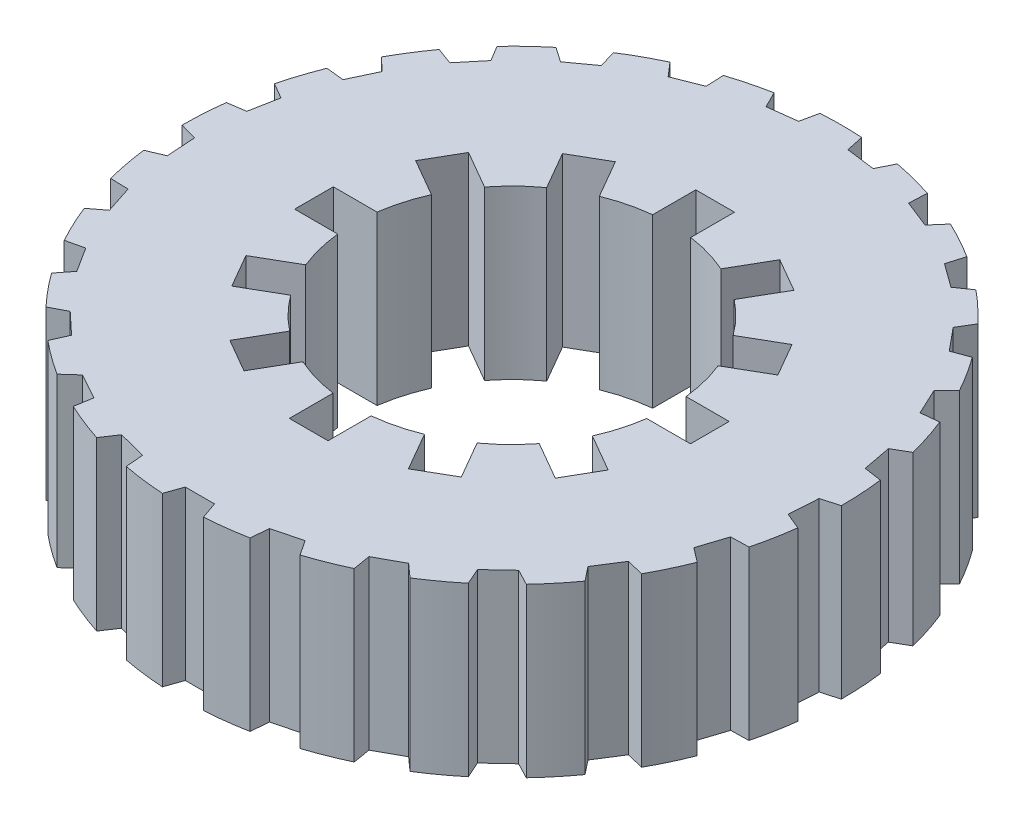
SolidWorks part; units mm, degrees
ref_plane "Front Plane" through (0, 0, 0) normal (0, 0, 1) x (1, 0, 0)
ref_plane "Top Plane" through (0, 0, 0) normal (0, 1, 0) x (1, 0, 0)
ref_plane "Right Plane" through (0, 0, 0) normal (1, 0, 0) x (0, 0, -1)
sketch "Sketch1" plane through (0, 0, 0) normal (0, 1, 0) x (1, 0, 0)
  circle A0 centre (0, 0) radius 37.465
extrude "Boss-Extrude1" add sketch "Sketch1" along normal blind 19.05
sketch "Sketch2" plane through (0, 0, 0) normal (0, -1, 0) x (1, 0, 0)
  line L10 (0, 37.465) -> (-2.36, 37.465)
  line L11 (0, 37.465) -> (2.36, 37.465)
  line L12 (0, 35.465) -> (-1.66, 35.465)
  line L13 (0, 35.465) -> (1.66, 35.465)
  line L14 (-2.36, 37.465) -> (-1.66, 35.465)
  line L15 (2.36, 37.465) -> (1.66, 35.465)
  circle A0 centre (0, 0) radius 37.465 construction
  dimension "D1" = 2.36
  dimension "D2" = 2.36
  dimension "D3" = 1.66
  dimension "D4" = 1.66
  dimension "D5" = 2
extrude "Cut-Extrude1" cut sketch "Sketch2" against normal blind 33
pattern_circular "CirPattern1" count 25 over 360 about axis through (0, 0, 0) along (0, 1, 0) of "Cut-Extrude1"
sketch "Sketch3" plane through (0, 19.05, 0) normal (0, 1, 0) x (1, 0, 0)
  line L16 (-1.9, 22.8) -> (-1.9, 17.8994)
  line L17 (0.3, 22.8) -> (-1.9, 22.8)
  line L18 (0.3, 22.8) -> (2.5, 22.8)
  line L19 (2.5, 22.8) -> (2.5, 17.8255)
  circle A1 centre (0, 0) radius 18
extrude "Cut-Extrude2" cut sketch "Sketch3" against normal blind 28 contours A1 region at (0, 19.05, 0)
extrude "Cut-Extrude8" cut sketch "Sketch3<7>" against normal blind 23 contours A1 region at (0.3056, 19.05, -20.3761)
sketch "Sketch3<7>" plane through (0, 19.05, 0) normal (0, 1, 0) x (1, 0, 0) same geometry as "Sketch3"
pattern_circular "CirPattern2" count 12 every 30 about axis through (0, 19.05, 0) along (0, 1, 0) of "Cut-Extrude8"
